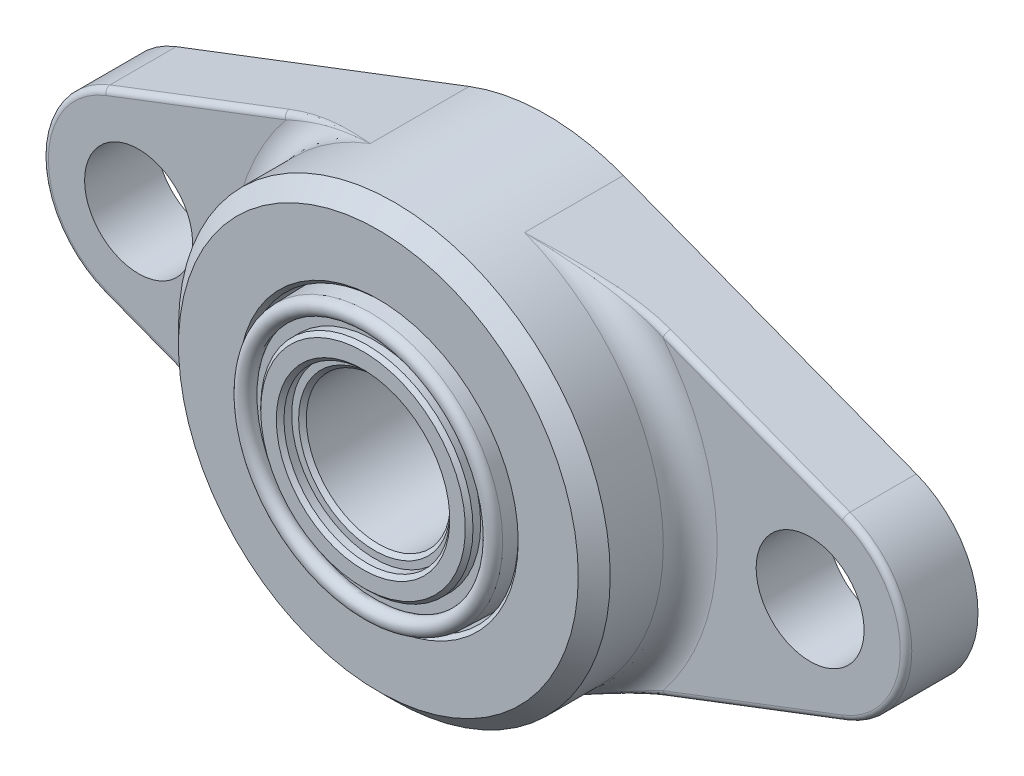
SolidWorks part; units mm, degrees
ref_plane "Front Plane" through (0, 0, 0) normal (0, 0, 1) x (1, 0, 0)
ref_plane "Top Plane" through (0, 0, 0) normal (0, 1, 0) x (1, 0, 0)
ref_plane "Right Plane" through (0, 0, 0) normal (1, 0, 0) x (0, 0, -1)
sketch "Sketch1" plane through (0, 0, 0) normal (0, 0, 1) x (1, 0, 0)
  line L0 (-22.225, 0) -> (22.225, 0) construction
  line L1 (0, 14.2875) -> (0, -14.2875) construction
  line L2 (-24.4929, 5.9312) -> (-5.1027, 13.3452)
  line L3 (5.1027, 13.3452) -> (24.4929, 5.9312)
  line L4 (24.4929, -5.9312) -> (5.1027, -13.3452)
  line L5 (-24.4929, -5.9312) -> (-5.1027, -13.3452)
  line L6 (-28.575, 0) -> (28.575, 0) construction
  line L7 (3.3748, 3.3748) -> (10.1028, 10.1028) construction
  circle A0 centre (-22.225, 0) radius 3.5719
  circle A1 centre (22.225, 0) radius 3.5719
  circle A2 centre (0, 0) radius 14.2875
  arc A3 (-24.4929, 5.9312) -> (-24.4929, -5.9312) centre (-22.225, 0) ccw
  arc A4 (24.4929, -5.9312) -> (24.4929, 5.9312) centre (22.225, 0) ccw
  circle A5 centre (0, 0) radius 4.7727
  circle A6 centre (0, 0) radius 9.0015 construction
  point P23 (6.365, 6.365)
  point P24 (0, 9.0015)
  point P25 (0, 4.7727)
  dimension "D1" = 4.2288
  dimension "D2" = 45
  dimension "Mounting Hole" = 7.1437
  dimension "ID" = 9.5453
  dimension "D4" = 18.003
  dimension "Mounting Center" = 44.45
  dimension "Height" = 28.575
  dimension "Length" = 57.15
  dimension "D3" = 9.5148
sketch "Sketch2" plane through (0, 0, 0) normal (1, 0, 0) x (0, 0, -1)
  line L0 (5.5562, 0) -> (-5.5562, 0) construction
  point P2 (0.7937, 0)
  point P4 (5.5562, 0)
  dimension "Width" = 11.1125
  dimension "flange thickness" = 4.7625
  dimension "Bearing Width" = 11.1125
sketch "Sketch3" plane through (0, 0, 0) normal (0, 0, 1) x (1, 0, 0)
  line L0 (-24.4929, 5.9312) -> (-5.1027, 13.3452) construction
  line L1 (5.1027, 13.3452) -> (24.4929, 5.9312) construction
  line L2 (24.4929, -5.9312) -> (5.1027, -13.3452) construction
  line L3 (-24.4929, -5.9312) -> (-5.1027, -13.3452) construction
  line L4 (-24.4929, 5.9312) -> (-5.1027, 13.3452)
  line L5 (5.1027, 13.3452) -> (24.4929, 5.9312)
  line L6 (24.4929, -5.9312) -> (5.1027, -13.3452)
  line L7 (-24.4929, -5.9312) -> (-5.1027, -13.3452)
  arc A0 (-24.4929, 5.9312) -> (-24.4929, -5.9312) centre (-22.225, 0) ccw construction
  circle A1 centre (-22.225, 0) radius 3.5719 construction
  circle A2 centre (0, 0) radius 14.2875 construction
  circle A3 centre (22.225, 0) radius 3.5719 construction
  arc A4 (24.4929, -5.9312) -> (24.4929, 5.9312) centre (22.225, 0) ccw construction
  arc A5 (-24.4929, 5.9312) -> (-24.4929, -5.9312) centre (-22.225, 0) ccw
  circle A6 centre (-22.225, 0) radius 3.5719
  arc A7 (-5.1027, -13.3452) -> (5.1027, -13.3452) centre (0, 0) ccw
  circle A8 centre (22.225, 0) radius 3.5719
  arc A9 (24.4929, -5.9312) -> (24.4929, 5.9312) centre (22.225, 0) ccw
  circle A10 centre (0, 0) radius 9.0015 construction
  circle A11 centre (0, 0) radius 9.0015
  arc A12 (5.1027, 13.3452) -> (-5.1027, 13.3452) centre (0, 0) ccw
extrude "Boss-Extrude1" add sketch "Sketch3" along normal up to vertex (-0.7937 mm away) from vertex at -5.5563 starting at point (0, 0, -5.5562)
sketch "Sketch4" plane through (0, 0, -0.7937) normal (0, 0, 1) x (1, 0, 0)
  circle A0 centre (0, 0) radius 14.2875 construction
  circle A1 centre (0, 0) radius 9.0015 construction
  circle A2 centre (0, 0) radius 14.2875
  circle A3 centre (0, 0) radius 9.0015
extrude "Boss-Extrude2" add sketch "Sketch4" along normal up to vertex (6.35 mm away) up to point (0, 0, 5.5562)
chamfer "Chamfer1" distance 0.254 angle 45 2 edges at (9.0015, 0, 5.5562) (9.0015, 0, -5.5562)
fillet "Fillet1" radius 1.778 2 edges
fillet "Fillet2" radius 0.381 10 edges at (8.643, 11.9916, -0.2459) (28.575, 0, -0.7937) (-8.643, 11.9916, -0.2459) (-28.575, 0, -0.7937) (-8.643, -11.9916, -0.2459) (8.643, -11.9916, -0.2459)
chamfer "Chamfer2" distance 1.0583 angle 45 1 edges at (14.2875, 0, 5.5562)
sketch "Sketch5" plane through (0, 0, 0) normal (1, 0, 0) x (0, 0, -1)
  line L0 (-5.5563, 4.7727) -> (5.5562, 4.7727)
  line L1 (-5.5563, 4.7727) -> (-5.5562, 9.0015)
  line L2 (-5.5562, 9.0015) -> (5.5562, 9.0015)
  line L3 (5.5562, 9.0015) -> (5.5562, 4.7727)
  line L4 (-5.5562, 0) -> (5.5562, 0) construction
  dimension "D1" = 11.1125
sketch "Sketch6" plane through (0, 0, 0) normal (1, 0, 0) x (0, 0, -1)
  line L0 (0, 9.0015) -> (-6.1163, 8.7879)
  line L1 (-5.8102, 7.7884) -> (-5.8102, 7.0263)
  line L2 (-5.8102, 7.0263) -> (-6.5723, 7.0263)
  line L3 (-6.5723, 7.0263) -> (-6.5723, 5.4886)
  line L4 (-5.8102, 4.7727) -> (-5.8102, 5.4886)
  line L5 (-5.8102, 5.4886) -> (-6.5723, 5.4886)
  line L6 (-5.5563, 4.7727) -> (5.5562, 4.7727) construction
  line L7 (-5.5563, 4.7727) -> (-5.5562, 9.0015) construction
  line L8 (-5.5562, 13.2292) -> (-5.5562, -13.2292) construction
  line L9 (-5.5562, 9.0015) -> (5.5562, 9.0015) construction
  line L10 (5.5086, 4.7727) -> (5.5086, 5.4886)
  line L11 (5.5086, 5.4886) -> (6.2706, 5.4886)
  line L12 (6.2706, 5.4886) -> (6.2706, 7.0263)
  line L13 (6.2706, 7.0263) -> (3.7306, 7.0263)
  line L14 (3.7306, 7.0263) -> (3.7306, 7.7884)
  line L15 (3.7306, 7.7884) -> (5.5562, 7.7884)
  line L16 (5.5562, 9.0015) -> (5.5562, 4.7727) construction
  line L17 (5.5562, 7.7884) -> (5.5562, 9.0015)
  line L18 (-5.8102, 4.7727) -> (5.5086, 4.7727)
  line L19 (0, 9.0015) -> (5.5562, 9.0015)
  line L20 (-5.5562, 0) -> (5.5562, 0) construction
  arc A0 (-6.1163, 8.7879) -> (-5.8102, 7.7884) centre (-6.0974, 8.247) ccw
  dimension "D1" = 1.016
  dimension "D2" = 0.254
  dimension "D3" = 2
  dimension "D4" = 4.2288
  dimension "D5" = 1.5378
  dimension "D6" = 10.9771
  dimension "D7" = 0.9995
  dimension "D8" = 0.7144
  dimension "D9" = 2.54
revolve "Revolve1" add sketch "Sketch6" angle 360 about L20
chamfer "Chamfer3" distance 0.254 angle 45 6 edges at (5.4886, 0, -6.2706) (7.0263, 0, -6.2706) (7.0263, 0, 6.5723) (5.4886, 0, 6.5723) (4.7727, 0, 5.8102) (4.7727, 0, -5.5086)
equation "\"D1@Chamfer2\"=(\"Width@Sketch2\"-\"flange thickness@Sketch2\")/6"
equation "\"D1@Sketch1\"=\"D3@Sketch1\"/2.25"
equation "\"D1@Sketch5\"=\"Bearing Width@Sketch2\""
equation "\"D5@Sketch6\"=\"D4@Sketch6\"/2.75"
equation "\"D6@Sketch6\"=\"ID@Sketch1\"*1.15"
equation "\"D7@Sketch6\"=\"D5@Sketch6\"*.65"
